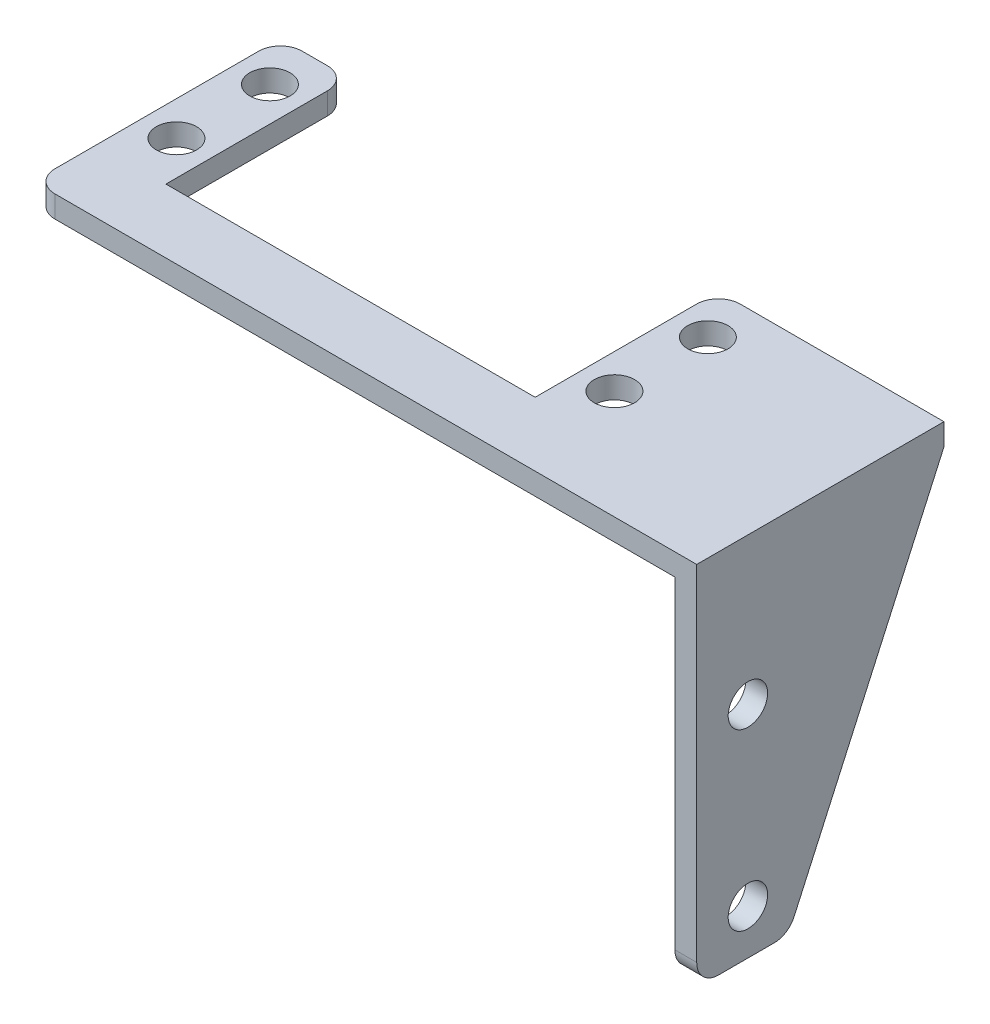
SolidWorks part; units mm, degrees
ref_plane "Front Plane" through (0, 0, 0) normal (0, 0, 1) x (1, 0, 0)
ref_plane "Top Plane" through (0, 0, 0) normal (0, 1, 0) x (1, 0, 0)
ref_plane "Right Plane" through (0, 0, 0) normal (1, 0, 0) x (0, 0, -1)
sketch "Sketch1" plane through (0, 0, 0) normal (0, 1, 0) x (1, 0, 0)
  line L0 (20.15, 0) -> (-20.15, 0)
  line L1 (-20.15, 0) -> (-20.15, 20)
  line L2 (-20.15, 20) -> (-27.65, 20)
  line L3 (-27.65, 20) -> (-27.65, -6.985)
  line L4 (-27.65, -6.985) -> (27.65, -6.985)
  line L5 (0, 0) -> (0, -6.985)
  line L6 (20.15, 20) -> (42.3837, 20)
  line L7 (42.3837, 20) -> (42.3837, -6.985)
  line L8 (20.15, 0) -> (20.15, 20)
  line L9 (27.65, -6.985) -> (42.3837, -6.985)
  circle A0 centre (-23.9, 15.1) radius 2.2
  circle A1 centre (-23.9, 4.9) radius 2.2
  circle A2 centre (23.9, 4.9) radius 2.2
  circle A3 centre (23.9, 15.1) radius 2.2
  point P0 (0, 0)
  dimension "D3" = 4.4
  dimension "D6" = 4.4
  dimension "D1" = 3.75
  dimension "D2" = 3.75
  dimension "D4" = 4.9
  dimension "D5" = 10.2
  dimension "D7" = 4.9
  dimension "D8" = 6.985
  dimension "D9" = 23.9
  dimension "D10" = 0
  dimension "D11" = 22.2338
extrude "Boss-Extrude1" add sketch "Sketch1" along normal blind 2.3813 contours L5 L0 L1 L2 L3 L4 A1 A0 | L8 L0 L5 L4 A2 A3 region at (27.3831, 0, -4.3765) region at (-0.3864, 0, 3.4925)
sketch "Sketch3" plane through (42.3837, 0, 0) normal (1, 0, 0) x (0, 0, -1)
  line L0 (20, 0) -> (3.015, -37.6187)
  line L1 (20, 2.3813) -> (-6.985, 2.3813)
  line L2 (20, 2.3813) -> (20, 0)
  line L3 (3.015, -37.6187) -> (-6.985, -37.6187)
  line L4 (-6.985, 2.3813) -> (-6.985, -37.6187)
  line L5 (-6.985, 2.3813) -> (-6.985, 0) construction
  point P10 (-6.985, 1.1906)
  dimension "D1" = 10
  dimension "D2" = 0
  dimension "D3" = 40
extrude "Boss-Extrude3" add sketch "Sketch3" along normal blind 2.3813
sketch "Sketch4" plane through (44.765, 0, 0) normal (1, 0, 0) x (0, 0, -1)
  line L0 (20, 2.3813) -> (-6.985, 2.3813) construction
  line L1 (-6.985, 2.3813) -> (-6.985, -37.6187) construction
  circle A0 centre (-1.397, -13.646) radius 2.1526
  circle A1 centre (-1.397, -32.696) radius 2.1526
  point P8 (0, 0)
  point P9 (0, 0)
  dimension "D4" = 4.3053
  dimension "D5" = 4.3053
  dimension "D1" = 16.0272
  dimension "D2" = 5.588
  dimension "D3" = 19.05
  dimension "D6" = 5.588
extrude "Cut-Extrude1" cut sketch "Sketch4" against normal up to surface (2.3813 mm away) up to face at (42.3837, -18.8094, -2.2613)
fillet "Fillet2" radius 2.3813 6 edges at (20.15, 1.1906, -20) (-20.15, 1.1906, -20) (-27.65, 1.1906, 6.985) (-27.65, 1.1906, -20) (43.5744, -37.6187, 6.985) (43.5744, -37.6187, -3.015)
